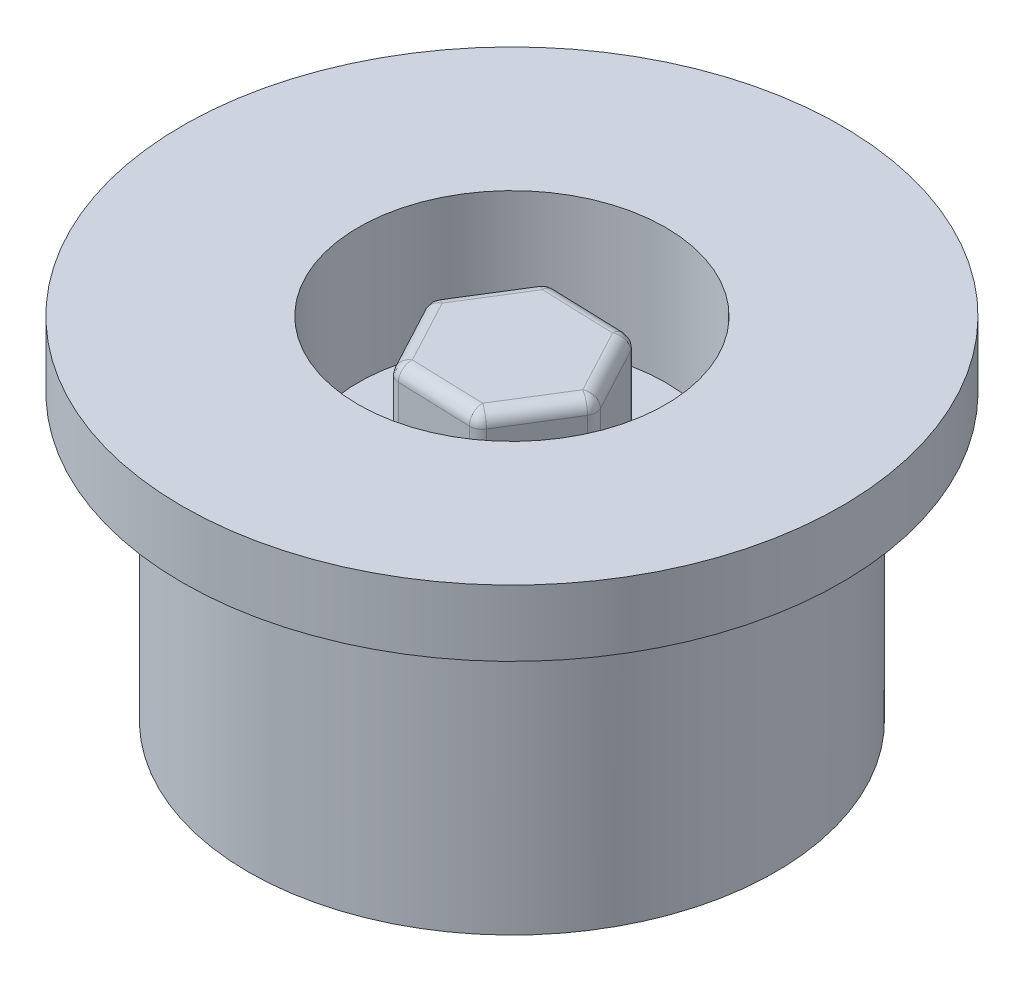
SolidWorks part; units mm, degrees
ref_plane "Front Plane" through (0, 0, 0) normal (0, 0, 1) x (1, 0, 0)
ref_plane "Top Plane" through (0, 0, 0) normal (0, 1, 0) x (1, 0, 0)
ref_plane "Right Plane" through (0, 0, 0) normal (1, 0, 0) x (0, 0, -1)
sketch "Sketch1" plane through (0, 0, 0) normal (0, 1, 0) x (1, 0, 0)
  circle A0 centre (0, 0) radius 2.3241
  circle A1 centre (0, 0) radius 6.8961
  dimension "D1" = 4.572
extrude "Boss-Extrude1" add sketch "Sketch1" along normal blind 2.794
sketch "Sketch2" plane through (0, 0, 0) normal (0, -1, 0) x (1, 0, 0)
  circle A0 centre (0, 0) radius 2.3241 construction
  circle A1 centre (0, 0) radius 2.3241
extrude "Boss-Extrude2" add sketch "Sketch2" against normal blind 0.762
sketch "Sketch3" plane through (0, 0.762, 0) normal (0, 1, 0) x (1, 0, 0)
  line L6 (-0.6403, 1.225) -> (0.7631, 1.179) construction
  line L7 (-1.3818, 0.0326) -> (-0.6403, 1.225) construction
  line L8 (-0.72, -1.2058) -> (-1.3818, 0.0326) construction
  line L9 (0.6834, -1.2518) -> (-0.72, -1.2058) construction
  line L10 (1.425, -0.0594) -> (0.6834, -1.2518) construction
  line L11 (0.7631, 1.179) -> (1.425, -0.0594) construction
  line L12 (-0.4958, 1.1567) -> (0.6144, 1.1203)
  line L13 (0.7762, 1.0197) -> (1.2998, 0.04)
  line L14 (1.2936, -0.1504) -> (0.707, -1.0937)
  line L15 (0.5389, -1.1835) -> (-0.5713, -1.1471)
  line L16 (-0.7331, -1.0465) -> (-1.2567, -0.0668)
  line L17 (-1.2505, 0.1236) -> (-0.6638, 1.0669)
  line L18 (-0.6057, 1.1603) -> (0.7244, 1.1167) construction
  line L19 (0.7244, 1.1167) -> (1.3517, -0.057) construction
  line L20 (-1.3085, 0.0302) -> (-0.6057, 1.1603) construction
  line L21 (-0.6812, -1.1435) -> (-1.3085, 0.0302) construction
  line L22 (0.6489, -1.1871) -> (-0.6812, -1.1435) construction
  line L23 (1.3517, -0.057) -> (0.6489, -1.1871) construction
  arc A0 (0.6144, 1.1203) -> (0.7762, 1.0197) centre (0.6082, 0.9299) cw
  arc A1 (-0.4958, 1.1567) -> (-0.6638, 1.0669) centre (-0.502, 0.9663) ccw
  arc A2 (-1.2567, -0.0668) -> (-1.2505, 0.1236) centre (-1.0887, 0.023) cw
  arc A3 (-0.5713, -1.1471) -> (-0.7331, -1.0465) centre (-0.5651, -0.9567) cw
  arc A4 (0.707, -1.0937) -> (0.5389, -1.1835) centre (0.5452, -0.9931) cw
  arc A5 (1.2998, 0.04) -> (1.2936, -0.1504) centre (1.1318, -0.0498) cw
  dimension "D2" = 0.1905
  dimension "D1" = 0.0635
extrude "Boss-Extrude3" add sketch "Sketch3" along normal blind 1.651
sketch "Sketch4" plane through (0, 0, 0) normal (0, -1, 0) x (1, 0, 0)
  circle A0 centre (0, 0) radius 1.651
  dimension "D1" = 3.302
sketch "Sketch5" plane through (0, 2.794, 0) normal (0, 1, 0) x (1, 0, 0)
  circle A0 centre (0, 0) radius 3.9875
  circle A1 centre (0, 0) radius 8.2069
  dimension "D1" = 7.975
extrude "Cut-Extrude1" cut sketch "Sketch5" against normal through all
sketch "Sketch6" plane through (0, 2.794, 0) normal (0, 1, 0) x (1, 0, 0)
  circle A0 centre (0, 0) radius 4.9875
  circle A1 centre (0, 0) radius 3.9875
  circle A2 centre (0, 0) radius 3.9875
  dimension "D1" = 0
  dimension "D2" = 1
extrude "Boss-Extrude4" add sketch "Sketch6" against normal blind 1
fillet "Fillet1" radius 0.2 12 edges at (1.038, 2.413, -0.5298) (1.3222, 2.413, 0.056) (1.0003, 2.413, 0.6221) (0.635, 2.413, 1.1611) (-0.0162, 2.413, 1.1653) (-0.6657, 2.413, 1.1185) (-0.9949, 2.413, 0.5567) (-1.2791, 2.413, -0.0292) (-0.9571, 2.413, -0.5952) (-0.5918, 2.413, -1.1343) (0.0593, 2.413, -1.1385) (0.7088, 2.413, -1.0917)
sketch "Sketch7" plane through (0, 0, 0) normal (0, -1, 0) x (1, 0, 0)
  circle A1 centre (0, 0) radius 3.9875
  circle A2 centre (0, 0) radius 3.9875
  dimension "D1" = 0
extrude "Boss-Extrude5" add sketch "Sketch7" along normal blind 2.5
